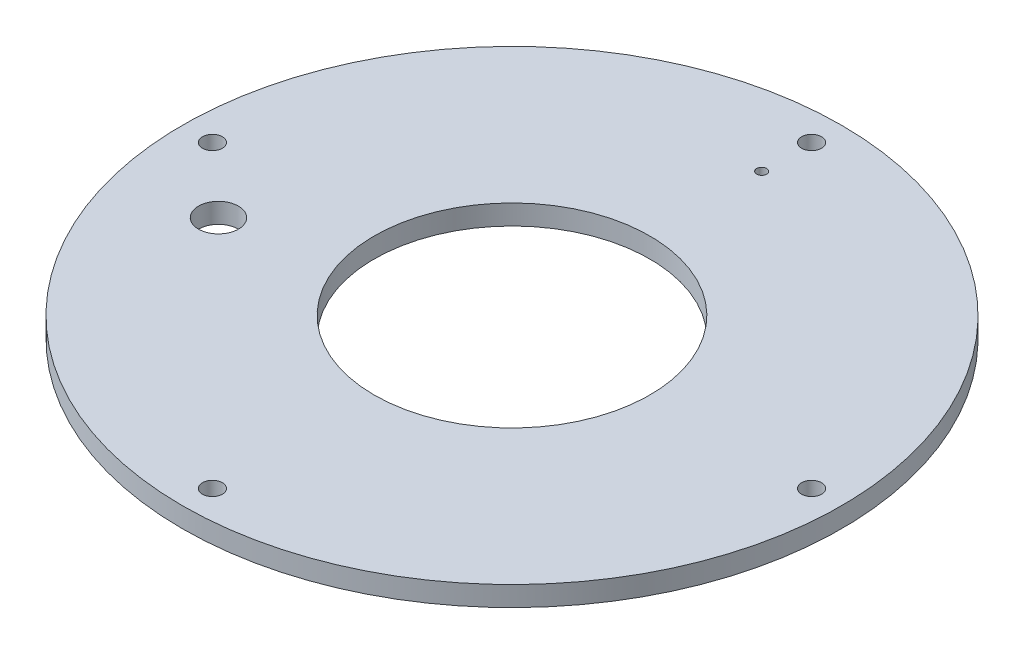
SolidWorks part; units mm, degrees
material "1060 Alloy"
ref_plane "Front Plane" through (0, 0, 0) normal (0, 0, 1) x (1, 0, 0)
ref_plane "Top Plane" through (0, 0, 0) normal (0, 1, 0) x (1, 0, 0)
ref_plane "Right Plane" through (0, 0, 0) normal (1, 0, 0) x (0, 0, -1)
sketch "Sketch1" plane through (0, 0, 0) normal (0, 1, 0) x (1, 0, 0)
  circle A0 centre (0, 0) radius 16.5
  circle A1 centre (0, 0) radius 6.9
  dimension "D1" = 33
  dimension "D2" = 13.8
extrude "Boss-Extrude1" add sketch "Sketch1" along normal blind 1
hole_wizard "CSK for M2 Flat Head Machine Screw1" positions "Sketch2" profile "Sketch3" countersink size "M2" standard "ANSI Metric" end condition through all
sketch "Sketch2" plane through (0, 0, 0) normal (0, -1, 0) x (-1, 0, 0)
  point P0 (0, -15)
  point P2 (-15, 0)
  point P4 (0, 15)
  point P28 (15, 0)
  dimension "D1" = 15
  dimension "D2" = 15
  dimension "D3" = 15
  dimension "D4" = 15
sketch "Sketch3" plane through (0, 0, 15) normal (1, 0, 0) x (0, 0, -1)
  line L0 (0, 0) -> (0, 1)
  line L1 (0, 1) -> (0.5, 1)
  line L2 (0.5, 1) -> (0.5, 0.2517)
  line L3 (0.5, 0.2517) -> (0.8, 0)
  line L5 (0.8, 0) -> (0, 0)
  line L6 (-0.5, 0.2517) -> (-0.8, 0) construction
  line L11 (0, -6.35) -> (0, 107.95) construction
  dimension "Thru Hole Dia." = 1
  dimension "Thru Hole Depth" = 1
  dimension "Near C'Sink Dia." = 1.6
  dimension "Near C'Sink Angle" = 100
sketch "Sketch4" plane through (0, 1, 0) normal (0, 1, 0) x (1, 0, 0)
  line L0 (0, 0) -> (-18.3501, -4.9169) construction
  line L1 (0, 0) -> (-15, 0) construction
  circle A0 centre (0, 12.5) radius 0.25
  circle A1 centre (-11.5911, -3.1058) radius 1
  dimension "D1" = 0.5
  dimension "D2" = 12.5
  dimension "D4" = 2
  dimension "D6" = 15
  dimension "D3" = 12
  dimension "D5" = 0
extrude "Cut-Extrude1" cut sketch "Sketch4" against normal through all both and the other way through all
